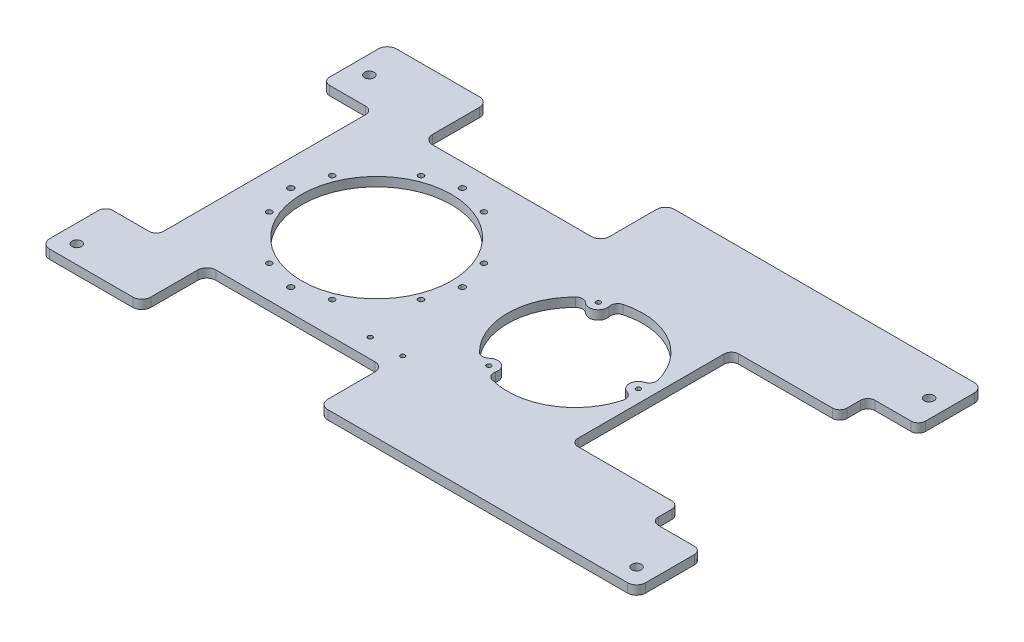
SolidWorks part; units mm, degrees
material "6061 Alloy"
ref_plane "Front Plane" through (0, 0, 0) normal (0, 0, 1) x (1, 0, 0)
ref_plane "Top Plane" through (0, 0, 0) normal (0, 1, 0) x (1, 0, 0)
ref_plane "Right Plane" through (0, 0, 0) normal (1, 0, 0) x (0, 0, -1)
sketch "Sketch1" plane through (0, 0, 0) normal (0, 1, 0) x (1, 0, 0)
  line L1 (0, 0) -> (330, 0)
  line L2 (0, 0) -> (0, 192)
  line L3 (0, 192) -> (330, 192)
  line L4 (330, 0) -> (330, 192)
  dimension "D1" = 192
  dimension "D2" = 330
extrude "Boss-Extrude1" add sketch "Sketch1" along normal blind 5
sketch "Sketch2" plane through (0, 5, 0) normal (0, 1, 0) x (1, 0, 0)
  line L0 (0, 0) -> (330, 0) construction
  line L1 (0, 0) -> (0, 192)
  line L2 (135.5, 96) -> (90, 96) construction
  line L3 (90, 96) -> (0, 96) construction
  line L4 (132.0365, 113.4121) -> (90, 96) construction
  circle A0 centre (90, 96) radius 50 construction
  circle A1 centre (90, 96) radius 45.5 construction
  circle A10 centre (132.0365, 113.4121) radius 1.5
  circle A11 centre (132.0365, 78.5879) radius 1.5
  circle A12 centre (107.4121, 53.9635) radius 1.5
  circle A13 centre (72.5879, 53.9635) radius 1.5
  circle A14 centre (47.9635, 78.5879) radius 1.5
  circle A15 centre (47.9635, 113.4121) radius 1.5
  circle A16 centre (72.5879, 138.0365) radius 1.5
  circle A17 centre (107.4121, 138.0365) radius 1.5
  point P21 (90, 96)
  point P30 (90, 96)
  dimension "D1" = 100
  dimension "D2" = 91
  dimension "D3" = 22.5
  dimension "D8" = 8
  dimension "D4" = 3
  dimension "D5" = 192
  dimension "D6" = 330
  dimension "D7" = 90
extrude "Cut-Extrude1" cut sketch "Sketch2" against normal through all and the other way through all contours A16 | A17 | A10 | A11 | A12 | A13 | A14 | A15
sketch "Sketch3" plane through (0, 5, 0) normal (0, 1, 0) x (1, 0, 0)
  line L0 (0, 0) -> (0, 192)
  line L1 (0, 0) -> (330, 0)
  line L2 (0, 0) -> (330, 0) construction
  circle A0 centre (90, 96) radius 41.5
  circle A1 centre (90, 96) radius 44 construction
  circle A5 centre (47.9635, 113.4121) radius 1.5 construction
  circle A6 centre (72.5879, 53.9635) radius 1.5 construction
  circle A7 centre (132.0365, 113.4121) radius 1.5 construction
  dimension "D1" = 83
  dimension "D2" = 330
  dimension "D3" = 192
extrude "Cut-Extrude2" cut sketch "Sketch3" against normal through all contours A0 region at (90, 5, -96)
hole_wizard "M5 Clearance Hole1" positions "Sketch13" profile "Sketch14" hole size "M5" standard "DIN"
sketch "Sketch13" plane through (0, 5, 0) normal (0, 1, 0) x (1, 0, 0)
  line L0 (0, 192) -> (0, 0) construction
  line L1 (330, 0) -> (330, 192) construction
  line L2 (10, 172) -> (320, 172) construction
  line L3 (320, 172) -> (320, 10) construction
  line L4 (320, 10) -> (10, 10) construction
  line L5 (10, 10) -> (10, 172) construction
  line L15 (330, 192) -> (0, 192) construction
  point P0 (10, 172)
  point P2 (10, 10)
  point P4 (320, 10)
  point P6 (320, 172)
  dimension "D1" = 10
  dimension "D2" = 10
  dimension "D3" = 10
  dimension "D4" = 10
  dimension "D5" = 162
  dimension "D6" = 162
  dimension "D7" = 20
sketch "Sketch14" plane through (10, 5, -172) normal (1, 0, 0) x (0, 0, 1)
  line L0 (0, 0) -> (0, 13.5323)
  line L1 (0, 13.5323) -> (2.65, 11.94)
  line L2 (2.65, 11.94) -> (2.65, 0)
  line L5 (2.65, 0) -> (0, 0)
  line L10 (0, 13.5323) -> (-2.65, 11.94) construction
  line L11 (0, -6.35) -> (0, 107.95) construction
  dimension "Hole Dia." = 5.3
  dimension "Hole Depth" = 11.94
  dimension "Drill Angle" = 118
hole_wizard "Tap Drill for M4 Tap1" positions "Sketch17" profile "Sketch18" hole size "M4" standard "DIN" end condition through all
sketch "Sketch17" plane through (0, 5, 0) normal (0, 1, 0) x (1, 0, 0)
  line L0 (132.0365, 113.4121) -> (132.0365, 78.5879)
  line L2 (132.0365, 96) -> (137.5, 96)
  line L3 (42.5, 96) -> (137.5, 96) construction
  circle A0 centre (90, 96) radius 47.5
  circle A1 centre (90, 96) radius 41.5 construction
  circle A3 centre (90, 96) radius 47.5 construction
  circle A6 centre (132.0365, 78.5879) radius 1.5 construction
  circle A7 centre (132.0365, 113.4121) radius 1.5 construction
  point P0 (137.5, 96)
  point P22 (90, 48.5)
  point P23 (42.5, 96)
  point P24 (90, 143.5)
  dimension "D1" = 95
  dimension "D2" = 4
sketch "Sketch18" plane through (137.5, 5, -96) normal (1, 0, 0) x (0, 0, 1)
  line L0 (0, 0) -> (0, 5)
  line L1 (0, 5) -> (1.65, 5)
  line L2 (1.65, 5) -> (1.65, 0)
  line L5 (1.65, 0) -> (0, 0)
  line L11 (0, -6.35) -> (0, 107.95) construction
  dimension "Thru Hole Dia." = 3.3
  dimension "Thru Hole Depth" = 5
sketch "Sketch19" plane through (0, 5, 0) normal (0, 1, 0) x (1, 0, 0)
  line L0 (0, 192) -> (0, 0) construction
  line L1 (0, 156) -> (28, 156)
  line L2 (0, 156) -> (0, 36)
  line L3 (0, 36) -> (28, 36)
  line L4 (28, 156) -> (28, 36)
  line L5 (330, 0) -> (330, 192) construction
  line L6 (330, 156) -> (302, 156)
  line L7 (330, 156) -> (330, 36)
  line L8 (330, 36) -> (302, 36)
  line L9 (302, 156) -> (302, 36)
  line L10 (0, 96) -> (28, 96) construction
  dimension "D1" = 120
  dimension "D2" = 28
extrude "Cut-Extrude3" cut sketch "Sketch19" against normal through all and the other way through all
sketch "Sketch21" plane through (0, 0, 0) normal (0, -1, 0) x (1, 0, 0)
  line L1 (302, -51.5) -> (242, -51.5)
  line L2 (302, -51.5) -> (302, -140.5)
  line L3 (302, -140.5) -> (242, -140.5)
  line L4 (242, -51.5) -> (242, -140.5)
  line L5 (302, -96) -> (302, -156) construction
  line L6 (302, -96) -> (302, -36) construction
  circle A0 centre (190.7932, -95.584) radius 40 construction
  dimension "D3" = 80
  dimension "D1" = 60
  dimension "D2" = 89
extrude "Cut-Extrude4" cut sketch "Sketch21" against normal through all
fillet "Fillet1" radius 4 12 edges at (330, 2.5, -36) (302, 2.5, -36) (330, 2.5, -156) (302, 2.5, -156) (28, 2.5, -156) (28, 2.5, -36) (0, 2.5, -36) (0, 2.5, -156) (242, 2.5, -51.5) (242, 2.5, -140.5) (302, 2.5, -140.5) (302, 2.5, -51.5)
sketch "Sketch23" plane through (0, 0, 0) normal (0, 0, 1) x (1, 0, 0)
  line L0 (131.5, 5) -> (48.5, 5) construction
  line L1 (131.5, 5) -> (48.5, 5)
  point P2 (165, 3)
  point P3 (90, 5)
ref_axis "Axis1" through (90, 5, 0) along (0, 0, -1)
sketch "Sketch24" plane through (242, 0, 0) normal (1, 0, 0) x (0, 0, -1)
  line L0 (137.5, 5) -> (54.5, 5) construction
  line L1 (137.5, 5) -> (54.5, 5)
  point P2 (96, 3)
ref_axis "Axis2" through (242, 3, -96) along (-1, 0, 0)
hole_wizard "Tap Drill for M3 Tap1" positions "Sketch25" profile "Sketch26" hole size "M3" standard "DIN" end condition up to next
sketch "Sketch25" plane through (0, 0, 0) normal (0, -1, 0) x (-1, 0, 0)
  line L0 (-242, 96) -> (-205.0032, 96) construction
  line L1 (-182.5, 126.3109) -> (-182.5, 65.6891) construction
  circle A0 centre (-200, 96) radius 35 construction
  circle A1 centre (-90, 96) radius 41.5 construction
  point P6 (-182.5, 65.6891)
  point P14 (-235, 96)
  point P15 (-182.5, 126.3109)
  dimension "D1" = 70
  dimension "D3" = 110
  dimension "D2" = 3
sketch "Sketch26" plane through (182.5, 0, -126.3109) normal (1, 0, 0) x (0, 0, -1)
  line L0 (0, 0) -> (0, 5)
  line L1 (0, 5) -> (1.25, 5)
  line L2 (1.25, 5) -> (1.25, 0)
  line L5 (1.25, 0) -> (0, 0)
  line L11 (0, -6.35) -> (0, 107.95) construction
  dimension "Thru Hole Dia." = 2.5
  dimension "Thru Hole Depth" = 5
sketch "Sketch29" plane through (0, 0, 0) normal (0, -1, 0) x (1, 0, 0)
  line L0 (200, -67.5) -> (90, -67.5)
  line L1 (145, -67.5) -> (145, -24.0733)
hole_wizard "Tap Drill for M3 Tap2" positions "Sketch30" profile "Sketch31" hole size "M3" standard "DIN" end condition up to next
sketch "Sketch30" plane through (0, 0, 0) normal (0, -1, 0) x (-1, 0, 0)
  point P0 (-154, 46.5)
  point P3 (-136, 46.5)
  point P9 (0, 0)
  point P10 (0, 0)
  dimension "D1" = 18
  dimension "D2" = 9
  dimension "D3" = 21
sketch "Sketch31" plane through (154, 0, -46.5) normal (1, 0, 0) x (0, 0, -1)
  line L0 (0, 0) -> (0, 5)
  line L1 (0, 5) -> (1.25, 5)
  line L2 (1.25, 5) -> (1.25, 0)
  line L5 (1.25, 0) -> (0, 0)
  line L11 (0, -6.35) -> (0, 107.95) construction
  dimension "Thru Hole Dia." = 2.5
  dimension "Thru Hole Depth" = 5
sketch "Sketch32" plane through (0, 0, 0) normal (0, -1, 0) x (1, 0, 0)
  circle A0 centre (200, -96) radius 35 construction
  circle A1 centre (200, -96) radius 37.5
  circle A2 centre (182.5, -65.6891) radius 5
  circle A3 centre (182.5, -126.3109) radius 5
  circle A4 centre (235, -96) radius 5
  point P0 (182.5, -65.6891)
  point P1 (182.5, -126.3109)
  point P2 (235, -96)
  dimension "D1" = 75
  dimension "D2" = 10
extrude "Cut-Extrude5" cut sketch "Sketch32" against normal through all contours A4 A1 A2 A3 region at (200, 0, -96)
fillet "Fillet2" radius 4 6 edges at (237.2321, 2.5, -91.5259) (237.2321, 2.5, -100.4741) (177.5092, 2.5, -126.0069) (185.2586, 2.5, -130.481) (185.2586, 2.5, -61.519) (177.5092, 2.5, -65.9931)
sketch "Sketch33" plane through (0, 0, 0) normal (0, -1, 0) x (1, 0, 0)
  line L0 (56, 0) -> (56, -40) construction
  line L1 (0, 0) -> (56, 0) construction
  line L2 (0, 0) -> (0, -40) construction
  line L3 (0, -40) -> (56, -40) construction
  line L4 (28, 0) -> (28, -40) construction
  line L5 (330, 0) -> (154, 0) construction
  line L6 (330, 0) -> (330, -55.5) construction
  line L7 (330, -55.5) -> (154, -55.5) construction
  line L8 (242, 0) -> (242, -55.5) construction
  line L9 (154, 0) -> (154, -55.5) construction
  line L10 (4, -36) -> (24, -36) construction
  line L11 (56, 0) -> (154, 0)
  line L12 (56, 0) -> (56, -36)
  line L13 (56, -36) -> (154, -36)
  line L14 (154, 0) -> (154, -36)
  line L15 (28, -96) -> (85.3759, -96) construction
  line L16 (28, -40) -> (28, -152) construction
  line L17 (56, -156) -> (154, -156)
  line L18 (154, -192) -> (154, -156)
  line L19 (56, -192) -> (154, -192)
  line L20 (56, -192) -> (56, -156)
extrude "Cut-Extrude6" cut sketch "Sketch33" against normal through all
fillet "Fillet3" radius 5 12 edges at (154, 2.5, -192) (154, 2.5, -156) (56, 2.5, -156) (56, 2.5, -192) (154, 2.5, 0) (154, 2.5, -36) (56, 2.5, 0) (56, 2.5, -36) (330, 2.5, -192) (330, 2.5, 0) (0, 2.5, 0) (0, 2.5, -192)
equation "\"D2@Sketch13\"=\"D1@Sketch13\""
equation "\"D3@Sketch13\"=\"D1@Sketch13\""
equation "\"D4@Sketch13\"=\"D1@Sketch13\""
equation "\"D6@Sketch13\"=\"D5@Sketch13\""
